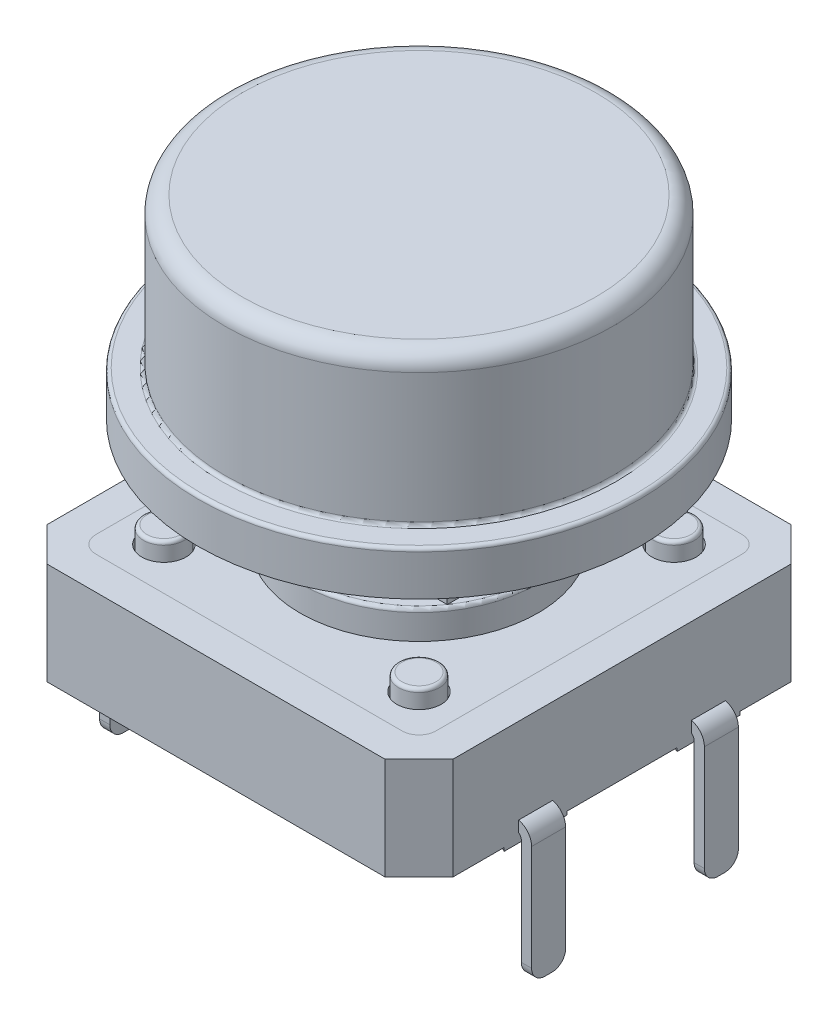
SolidWorks part; units mm, degrees
other "Plastic Button"
other "Button Body"
other "Metal Cover"
other "Connection 2"
other "Connection 1"
ref_plane "Front Plane" through (0, 0, 0) normal (0, 0, 1) x (1, 0, 0)
ref_plane "Top Plane" through (0, 0, 0) normal (0, 1, 0) x (1, 0, 0)
ref_plane "Right Plane" through (0, 0, 0) normal (1, 0, 0) x (0, 0, -1)
sketch "Sketch1" plane through (0, 0, 0) normal (0, 1, 0) x (1, 0, 0)
  line L0 (-5.97, 0) -> (5.97, 0) construction
  line L1 (-5.97, 5.97) -> (5.97, 5.97)
  line L2 (-5.97, 5.97) -> (-5.97, -5.97)
  line L3 (-5.97, -5.97) -> (5.97, -5.97)
  line L4 (5.97, 5.97) -> (5.97, -5.97)
  line L6 (-6.35, 2.54) -> (6.35, 2.54) construction
  line L7 (-6.35, 2.54) -> (-6.35, -2.54) construction
  line L8 (-6.35, -2.54) -> (6.35, -2.54) construction
  line L9 (6.35, 2.54) -> (6.35, -2.54) construction
  line L10 (-6.35, 2.54) -> (6.35, -2.54) construction
  line L11 (-6.35, -2.54) -> (6.35, 2.54) construction
  circle A0 centre (-6.35, 2.54) radius 1 construction
  circle A1 centre (6.35, 2.54) radius 1 construction
  circle A2 centre (6.35, -2.54) radius 1 construction
  circle A3 centre (-6.35, -2.54) radius 1 construction
  point P6 (0, 0)
  dimension "D5" = 2
  dimension "D1" = 11.94
  dimension "D2" = 11.94
  dimension "D3" = 12.7
  dimension "D4" = 5.08
extrude "Boss-Extrude1" add sketch "Sketch1" against normal blind 3
sketch "Sketch2" plane through (0, 0, 0) normal (0, 1, 0) x (1, 0, 0)
  line L1 (-5, 5) -> (5, 5)
  line L2 (-5, 5) -> (-5, -5)
  line L3 (-5, -5) -> (5, -5)
  line L4 (5, 5) -> (5, -5)
  line L5 (-5, 5) -> (5, -5) construction
  line L6 (-5, -5) -> (5, 5) construction
  point P0 (0, 0)
  dimension "D1" = 10
extrude "Cut-Extrude1" cut sketch "Sketch2" against normal blind 0.5
fillet "Fillet1" radius 0.5 4 edges at (-5, -0.25, 5) (5, -0.25, 5) (5, -0.25, -5) (-5, -0.25, -5)
chamfer "Chamfer1" distance 1 angle 45 4 edges at (5.97, -1.5, -5.97) (-5.97, -1.5, -5.97) (-5.97, -1.5, 5.97) (5.97, -1.5, 5.97)
sketch "Sketch3" plane through (0, -0.5, 0) normal (0, 1, 0) x (1, 0, 0)
  line L4 (-5, 4.5) -> (-5, -4.5)
  line L5 (-4.5, -5) -> (4.5, -5)
  line L6 (5, -4.5) -> (5, 4.5)
  line L7 (4.5, 5) -> (-4.5, 5)
  line L8 (-5, 4.5) -> (-5, -4.5)
  line L9 (-4.5, -5) -> (4.5, -5)
  line L10 (5, -4.5) -> (5, 4.5)
  line L11 (4.5, 5) -> (-4.5, 5)
  arc A4 (-5, -4.5) -> (-4.5, -5) centre (-4.5, -4.5) ccw
  arc A5 (4.5, -5) -> (5, -4.5) centre (4.5, -4.5) ccw
  arc A6 (5, 4.5) -> (4.5, 5) centre (4.5, 4.5) ccw
  arc A7 (-4.5, 5) -> (-5, 4.5) centre (-4.5, 4.5) ccw
  arc A8 (-5, -4.5) -> (-4.5, -5) centre (-4.5, -4.5) ccw
  arc A9 (4.5, -5) -> (5, -4.5) centre (4.5, -4.5) ccw
  arc A10 (5, 4.5) -> (4.5, 5) centre (4.5, 4.5) ccw
  arc A11 (-4.5, 5) -> (-5, 4.5) centre (-4.5, 4.5) ccw
  dimension "D1" = 0
extrude "Boss-Extrude2" add sketch "Sketch3" along normal blind 0.5 separate body
sketch "Sketch4" plane through (0, 0, 0) normal (0, 1, 0) x (1, 0, 0)
  line L1 (-3.75, 3.75) -> (3.75, 3.75) construction
  line L2 (-3.75, 3.75) -> (-3.75, -3.75) construction
  line L3 (-3.75, -3.75) -> (3.75, -3.75) construction
  line L4 (3.75, 3.75) -> (3.75, -3.75) construction
  line L5 (-3.75, 3.75) -> (3.75, -3.75) construction
  line L6 (-3.75, -3.75) -> (3.75, 3.75) construction
  circle A0 centre (0, 0) radius 3.5
  circle A1 centre (-3.75, 3.75) radius 0.65
  circle A2 centre (3.75, 3.75) radius 0.65
  circle A3 centre (3.75, -3.75) radius 0.65
  circle A4 centre (-3.75, -3.75) radius 0.65
  dimension "D1" = 7.5
  dimension "D2" = 7
  dimension "D3" = 1.3
extrude "Cut-Extrude2" cut sketch "Sketch4" against normal up to surface (0.5 mm away) up to face at (0, -0.5, 0)
sketch "Sketch5" plane through (0, -0.5, 0) normal (0, 1, 0) x (1, 0, 0)
  circle A0 centre (0, 0) radius 3.45 construction
  circle A1 centre (-3.75, 3.75) radius 0.6
  circle A2 centre (3.75, 3.75) radius 0.6
  circle A3 centre (3.75, -3.75) radius 0.6
  circle A4 centre (-3.75, -3.75) radius 0.6
  dimension "D1" = 6.9
  dimension "D2" = 1.2
extrude "Boss-Extrude3" add sketch "Sketch5" along normal blind 1
sketch "Sketch6" plane through (0, -0.5, 0) normal (0, 1, 0) x (1, 0, 0)
  circle A0 centre (0, 0) radius 3.45 construction
  circle A1 centre (0, 0) radius 3.45
extrude "Boss-Extrude4" add sketch "Sketch6" along normal blind 1.3
sketch "Sketch7" plane through (0, 0.8, 0) normal (0, 1, 0) x (1, 0, 0)
  line L1 (-1.35, 1.35) -> (1.35, 1.35)
  line L2 (-1.35, 1.35) -> (-1.35, -1.35)
  line L3 (-1.35, -1.35) -> (1.35, -1.35)
  line L4 (1.35, 1.35) -> (1.35, -1.35)
  line L5 (-1.35, 1.35) -> (1.35, -1.35) construction
  line L6 (-1.35, -1.35) -> (1.35, 1.35) construction
  point P0 (0, 0)
  dimension "D1" = 2.7
extrude "Boss-Extrude5" add sketch "Sketch7" along normal blind 1.3
sketch "Sketch8" plane through (0, 2.1, 0) normal (0, 1, 0) x (1, 0, 0)
  line L0 (0, 1.925) -> (0, -1.925) construction
  line L1 (-1.725, 1.925) -> (1.725, 1.925)
  line L2 (-1.925, 1.725) -> (-1.925, -1.725)
  line L3 (-1.725, -1.925) -> (1.725, -1.925)
  line L4 (1.925, 1.725) -> (1.925, -1.725)
  arc A0 (-1.725, 1.925) -> (-1.925, 1.725) centre (-1.725, 1.725) ccw
  arc A1 (-1.925, -1.725) -> (-1.725, -1.925) centre (-1.725, -1.725) ccw
  arc A2 (1.725, -1.925) -> (1.925, -1.725) centre (1.725, -1.725) ccw
  arc A3 (1.725, 1.925) -> (1.925, 1.725) centre (1.725, 1.725) cw
  dimension "D3" = 0.2
  dimension "D1" = 3.85
  dimension "D2" = 3.85
extrude "Boss-Extrude6" add sketch "Sketch8" along normal blind 2.1
sketch "Sketch9" plane through (0, 4.2, 0) normal (0, 1, 0) x (1, 0, 0)
  circle A0 centre (0, 0) radius 1
  dimension "D1" = 2
extrude "Cut-Extrude3" cut sketch "Sketch9" against normal blind 1.5
sketch "Sketch10" plane through (0, 0, 0) normal (1, 0, 0) x (0, 0, -1)
  line L0 (0, 0) -> (0, -3) construction
  line L1 (-4.97, -3) -> (4.97, -3) construction
  line L2 (0, 0) -> (0, 3.2) construction
  line L3 (0, 3.2) -> (-6.5, 3.2)
  line L4 (-6.5, 3.2) -> (-6.5, 4.4)
  line L5 (-6.4, 4.5) -> (-5.7, 4.5)
  line L6 (-5.7, 4.5) -> (-5.7, 8.4)
  line L7 (-5.2, 8.9) -> (0, 8.9)
  line L8 (0, 8.9) -> (0, 3.2)
  arc A0 (-5.7, 8.4) -> (-5.2, 8.9) centre (-5.2, 8.4) cw
  arc A1 (-6.5, 4.4) -> (-6.4, 4.5) centre (-6.4, 4.4) cw
  dimension "D1" = 6.5
  dimension "D6" = 0.5
  dimension "D7" = 0.1
  dimension "D2" = 5.7
  dimension "D3" = 1.3
  dimension "D4" = 3.2
  dimension "D5" = 5.7
revolve "Revolve1" add sketch "Sketch10" angle 360 about L8
sketch "Sketch11" plane through (0, 3.2, 0) normal (0, -1, 0) x (1, 0, 0)
  circle A0 centre (0, 0) radius 5
  dimension "D1" = 10
extrude "Cut-Extrude4" cut sketch "Sketch11" against normal blind 4
sketch "Sketch12" plane through (0, 7.2, 0) normal (0, -1, 0) x (1, 0, 0)
  line L0 (-1.55, 0) -> (1.55, 0) construction
  line L2 (1.55, 1.92) -> (2.75, 1.92)
  line L3 (1.55, 1.92) -> (1.55, -1.92)
  line L4 (1.55, -1.92) -> (2.75, -1.92)
  line L5 (2.75, 1.92) -> (2.75, -1.92)
  line L6 (-1.55, 1.92) -> (-2.75, 1.92)
  line L7 (-1.55, 1.92) -> (-1.55, -1.92)
  line L8 (-1.55, -1.92) -> (-2.75, -1.92)
  line L9 (-2.75, 1.92) -> (-2.75, -1.92)
  dimension "D1" = 5.5
  dimension "D2" = 3.84
  dimension "D3" = 1.2
extrude "Boss-Extrude7" add sketch "Sketch12" along normal offset from surface (6.4 mm away) 2.4 up to face at (0, 3.2, -5) offset beyond the face yes
sketch "Sketch13" plane through (0, 0, 1.92) normal (0, 0, 1) x (1, 0, 0)
  line L0 (-1.55, 0.8) -> (-1.55, 7.2) construction
  line L1 (-1.55, 2) -> (-2.05, 2)
  line L2 (-1.55, 2) -> (-1.55, 7.2)
  line L3 (-1.55, 7.2) -> (-2.05, 7.2)
  line L4 (-2.05, 2) -> (-2.05, 7.2)
  line L5 (-5, 7.2) -> (5, 7.2) construction
  line L6 (1.55, 0.8) -> (1.55, 7.2) construction
  line L7 (1.55, 2) -> (2.05, 2)
  line L8 (1.55, 2) -> (1.55, 7.2)
  line L9 (1.55, 7.2) -> (2.05, 7.2)
  line L10 (2.05, 2) -> (2.05, 7.2)
  line L11 (-2.75, 0.8) -> (-1.55, 0.8) construction
  line L12 (-2.75, 0.8) -> (-2.75, 7.2) construction
  dimension "D1" = 0.7
  dimension "D2" = 1.2
extrude "Cut-Extrude5" cut sketch "Sketch13" against normal up to surface (3.84 mm away) up to face at (-2.15, 4, -1.92)
fillet "Fillet2" radius 0.5 2 edges at (-1.55, 0.8, 0) (1.55, 0.8, 0)
fillet "Fillet3" radius 0.6 2 edges at (1.55, 2, 0) (-1.55, 2, 0)
fillet "Fillet4" radius 0.1 5 edges at (0, 0.8, 3.45) (-3.75, 0.5, 4.35) (3.75, 0.5, 4.35) (3.75, 0.5, -3.15) (-3.75, 0.5, -3.15)
sketch "Sketch14" plane through (0, 7.2, 0) normal (0, -1, 0) x (1, 0, 0)
  line L0 (0, 1.93) -> (0, -1.93) construction
  line L2 (-1, 2.75) -> (1, 2.75)
  line L3 (-1, 2.75) -> (-1, 1.93)
  line L4 (-1, 1.93) -> (1, 1.93)
  line L5 (1, 2.75) -> (1, 1.93)
  line L10 (-1, -1.93) -> (1, -1.93)
  line L11 (-1, -1.93) -> (-1, -2.75)
  line L12 (-1, -2.75) -> (1, -2.75)
  line L13 (1, -1.93) -> (1, -2.75)
  dimension "D1" = 2
  dimension "D2" = 0.82
  dimension "D3" = 5.5
extrude "Boss-Extrude8" add sketch "Sketch14" along normal blind 5.36
fillet "Fillet5" radius 0.1 1 edges at (0, 4.5, 5.7)
sketch "Sketch15" plane through (0, 7.2, 0) normal (0, -1, 0) x (1, 0, 0)
  line L0 (0, -2.75) -> (0, 2.75) construction
  line L1 (1, 2.75) -> (-1, 2.75) construction
  line L2 (2.75, 0) -> (-2.75, 0) construction
  line L3 (-0.3, 5.25) -> (0.3, 5.25)
  line L4 (-0.3, 5.25) -> (-0.3, 2.75)
  line L5 (-0.3, 2.75) -> (0.3, 2.75)
  line L6 (0.3, 5.25) -> (0.3, 2.75)
  line L7 (-0.3, -2.75) -> (0.3, -2.75)
  line L8 (-0.3, -2.75) -> (-0.3, -5.25)
  line L9 (-0.3, -5.25) -> (0.3, -5.25)
  line L10 (0.3, -2.75) -> (0.3, -5.25)
  line L11 (2.75, -1.92) -> (2.75, 1.92) construction
  line L13 (2.75, 0.3) -> (5.25, 0.3)
  line L14 (2.75, 0.3) -> (2.75, -0.3)
  line L15 (2.75, -0.3) -> (5.25, -0.3)
  line L16 (5.25, 0.3) -> (5.25, -0.3)
  line L17 (-2.75, 0.3) -> (-5.25, 0.3)
  line L18 (-2.75, 0.3) -> (-2.75, -0.3)
  line L19 (-2.75, -0.3) -> (-5.25, -0.3)
  line L20 (-5.25, 0.3) -> (-5.25, -0.3)
  dimension "D1" = 2.5
  dimension "D2" = 0.6
extrude "Boss-Extrude9" add sketch "Sketch15" along normal up to surface (4 mm away) up to face at (0, 3.2, -5)
ref_plane "Plane1" through (0, 0, 2.54) normal (0, 0, 1) x (1, 0, 0)
sketch "Sketch16" plane through (0, 0, 2.54) normal (0, 0, 1) x (1, 0, 0)
  line L0 (0, 0) -> (0, -2.5) construction
  line L1 (-4.97, 0) -> (4.97, 0) construction
  line L2 (-5.85, -2.5) -> (5.85, -2.5)
  line L3 (0, -2.5) -> (0, -3) construction
  line L4 (-4.97, -3) -> (4.97, -3) construction
  line L5 (6.35, -3) -> (6.35, -6.5)
  line L6 (6.35, -6.5) -> (6.05, -6.5)
  line L7 (6.05, -6.5) -> (6.05, -3)
  line L8 (5.85, -2.8) -> (-5.85, -2.8)
  line L9 (-6.05, -3) -> (-6.05, -6.5)
  line L10 (-6.05, -6.5) -> (-6.35, -6.5)
  line L11 (-6.35, -6.5) -> (-6.35, -3)
  arc A0 (-5.85, -2.8) -> (-6.05, -3) centre (-5.85, -3) ccw
  arc A1 (6.05, -3) -> (5.85, -2.8) centre (5.85, -3) ccw
  arc A2 (-5.85, -2.5) -> (-6.35, -3) centre (-5.85, -3) ccw
  arc A3 (5.85, -2.5) -> (6.35, -3) centre (5.85, -3) cw
  dimension "D5" = 0.2
  dimension "D6" = 0.5
  dimension "D1" = 0.5
  dimension "D2" = 0.3
  dimension "D3" = 0.3
  dimension "D4" = 4
  dimension "D7" = 12.7
extrude "Boss-Extrude10" add sketch "Sketch16" along normal mid plane 1 separate body
mirror "Mirror1" about plane through (0, 0, 0) normal (0, 0, 1) of bodies 116
sketch "Sketch18" plane through (0, -3, 0) normal (0, -1, 0) x (1, 0, 0)
  line L0 (-5.97, -4.97) -> (-5.97, 4.97) construction
  line L1 (-5.97, -3.465) -> (-5.97, -1.615)
  line L2 (5.97, 4.97) -> (5.97, -4.97) construction
  line L3 (5.97, 3.465) -> (5.97, 1.615)
  line L4 (5.97, -1.615) -> (5.97, -3.465)
  line L5 (-5.97, 1.615) -> (-5.97, 3.465)
  line L6 (-5, 0) -> (5, 0) construction
  line L7 (-3, 5) -> (3, 5)
  line L8 (-5, 3) -> (-5, -3)
  line L9 (-3, -5) -> (3, -5)
  line L10 (5, 3) -> (5, -3)
  circle A0 centre (-6.35, 2.54) radius 1 construction
  arc A1 (-5.97, 1.615) -> (-5.97, 3.465) centre (-6.35, 2.54) ccw
  circle A2 centre (6.35, 2.54) radius 1 construction
  arc A3 (5.97, 3.465) -> (5.97, 1.615) centre (6.35, 2.54) ccw
  circle A4 centre (-6.35, -2.54) radius 1 construction
  arc A5 (-5.97, -3.465) -> (-5.97, -1.615) centre (-6.35, -2.54) ccw
  circle A6 centre (6.35, -2.54) radius 1 construction
  arc A7 (5.97, -1.615) -> (5.97, -3.465) centre (6.35, -2.54) ccw
  arc A8 (-3, 5) -> (-5, 3) centre (-3, 3) ccw
  arc A9 (-5, -3) -> (-3, -5) centre (-3, -3) ccw
  arc A10 (3, -5) -> (5, -3) centre (3, -3) ccw
  arc A11 (3, 5) -> (5, 3) centre (3, 3) cw
  dimension "D3" = 2
  dimension "D1" = 10
  dimension "D2" = 10
extrude "Boss-Extrude12" add sketch "Sketch18" along normal blind 0.1
sketch "Sketch19" plane through (0, -3.1, 0) normal (0, -1, 0) x (1, 0, 0)
  line L0 (-3, 5) -> (-3, 3)
  line L1 (-3, 3) -> (-5, 3)
  line L2 (3, 5) -> (3, 3)
  line L3 (3, 3) -> (5, 3)
  line L4 (-5, 3) -> (-5, -3)
  line L5 (-3, -5) -> (3, -5)
  line L6 (5, -3) -> (5, 3)
  line L7 (3, 5) -> (-3, 5)
  line L8 (-5, 3) -> (-5, -3)
  line L9 (-3, -5) -> (3, -5)
  line L10 (5, -3) -> (5, 3)
  line L11 (3, 5) -> (-3, 5)
  line L12 (-5, -3) -> (-3, -3)
  line L13 (-3, -3) -> (-3, -5)
  line L14 (3, -5) -> (3, -3)
  line L15 (3, -3) -> (5, -3)
  line L17 (-3, 3) -> (3, 3) construction
  line L18 (-3, 3) -> (-3, -3) construction
  line L19 (-3, -3) -> (3, -3) construction
  line L20 (3, 3) -> (3, -3) construction
  line L21 (-3, 3) -> (3, -3) construction
  line L22 (-3, -3) -> (3, 3) construction
  arc A4 (-3, 5) -> (-5, 3) centre (-3, 3) ccw
  arc A5 (-5, -3) -> (-3, -5) centre (-3, -3) ccw
  arc A6 (3, -5) -> (5, -3) centre (3, -3) ccw
  arc A7 (5, 3) -> (3, 5) centre (3, 3) ccw
  point P0 (0, 0)
  dimension "D1" = 0
extrude "Cut-Extrude6" cut sketch "Sketch19" against normal up to surface (0.1 mm away) up to face at (0, -3, 0)
fillet "Fillet6" radius 0.4 4 edges at (-6.2, -6.5, 3.04) (-6.2, -6.5, 2.04) (6.2, -6.5, 2.04) (6.2, -6.5, 3.04)
fillet "Fillet7" radius 0.4 4 edges at (-6.2, -6.5, -3.04) (-6.2, -6.5, -2.04) (6.2, -6.5, -2.04) (6.2, -6.5, -3.04)
